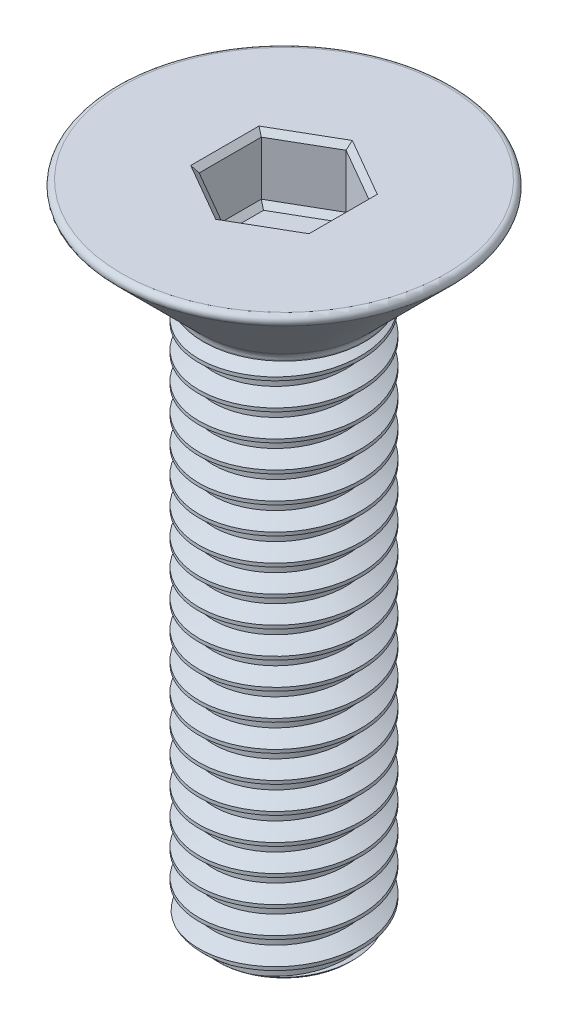
SolidWorks part; units mm, degrees
material "AISI Type A2 Tool Steel"
ref_plane "Front Plane" through (0, 0, 0) normal (0, 0, 1) x (1, 0, 0)
ref_plane "Top Plane" through (0, 0, 0) normal (0, 1, 0) x (1, 0, 0)
ref_plane "Right Plane" through (0, 0, 0) normal (1, 0, 0) x (0, 0, -1)
sketch "Sketch1" plane through (0, 0, 0) normal (0, 1, 0) x (1, 0, 0)
  circle A0 centre (0, 0) radius 1.5
  dimension "D1" = 3
extrude "Boss-Extrude1" add sketch "Sketch1" along normal blind 10.14
thread "Thread1" pitch 0.5 method cut profile "Thread Profile1" start angle 0, offset 1, length 0, pitch 0.5, diameter 3
ref_plane "Plane1" through (-1.5, 11.14, 0) normal (0, 0, 1) x (-1, 0, 0)
sketch "Thread Profile1" plane through (-1.5, 11.14, 0) normal (0, 0, 1) x (-1, 0, 0)
  line L0 (0, 0) -> (0, 0.5) construction
  line L11 (0, 0) -> (0, 0.4375)
  line L12 (0, 0.4375) -> (-0.2706, 0.2812)
  line L13 (-0.2706, 0.2812) -> (-0.2706, 0.1562)
  line L15 (-0.2706, 0.1562) -> (0, 0)
  line L17 (-0.2706, 0.2187) -> (0, 0.2187) construction
  point P2 (0, 0)
  dimension "Pitch" = 0.5
  dimension "Profile_Angle" = 60
  dimension "Profile_Land" = 0.125
  dimension "Profile_Height" = 0.2706
sketch "Sketch5" plane through (0, 10.14, 0) normal (0, 1, 0) x (1, 0, 0)
  circle A0 centre (0, 0) radius 1.5
  dimension "D1" = 3
extrude "Boss-Extrude2" add sketch "Sketch5" along normal blind 0.1
sketch "Sketch6" plane through (0, 10.24, 0) normal (0, 1, 0) x (1, 0, 0)
  circle A0 centre (0, 0) radius 1.5
  dimension "D1" = 3
extrude "Boss-Extrude3" add sketch "Sketch6" along normal blind 1.76 draft 45 draft outward yes
sketch "Sketch7" plane through (0, 0, 0) normal (0, 0, 1) x (1, 0, 0)
  line L0 (0, 0) -> (0, 0.1997) construction
  line L1 (0, 0) -> (1.51, 0) construction
  line L2 (1.51, 0) -> (1.51, 0.3)
  line L3 (1.51, 0.3) -> (1.21, 0)
  line L4 (1.21, 0) -> (1.51, 0)
  dimension "D1" = 45
  dimension "D2" = 0.3
  dimension "D3" = 1.51
revolve "Cut-Revolve1" cut sketch "Sketch7" angle 360 about L0
fillet "Fillet1" radius 0.1 1 edges at (0, 12, 3.26)
fillet "Fillet2" radius 0.2 1 edges at (0, 10.24, 1.5)
sketch "Sketch8" plane through (0, 12, 0) normal (0, 1, 0) x (1, 0, 0)
  line L1 (0, 1.1547) -> (-1, 0.5774)
  line L2 (-1, 0.5774) -> (-1, -0.5774)
  line L3 (-1, -0.5774) -> (0, -1.1547)
  line L4 (0, -1.1547) -> (1, -0.5774)
  line L5 (1, -0.5774) -> (1, 0.5774)
  line L6 (1, 0.5774) -> (0, 1.1547)
  circle A0 centre (0, 0) radius 1 construction
  dimension "D1" = 2
extrude "Cut-Extrude1" cut sketch "Sketch8" against normal blind 1.1
chamfer "Chamfer1" distance 0.1 angle 45 6 edges at (-1, 12, 0) (-0.5, 12, 0.866) (0.5, 12, 0.866) (1, 12, 0) (0.5, 12, -0.866) (-0.5, 12, -0.866)
sketch "Sketch9" plane through (0, 10.9, 0) normal (0, 1, 0) x (1, 0, 0)
  line L1 (0, 1.1547) -> (-1, 0.5774)
  line L2 (-1, 0.5774) -> (-1, -0.5774)
  line L3 (-1, -0.5774) -> (0, -1.1547)
  line L4 (0, -1.1547) -> (1, -0.5774)
  line L5 (1, -0.5774) -> (1, 0.5774)
  line L6 (1, 0.5774) -> (0, 1.1547)
  circle A0 centre (0, 0) radius 1 construction
extrude "Cut-Extrude2" cut sketch "Sketch9" against normal blind 0.1 draft 45
